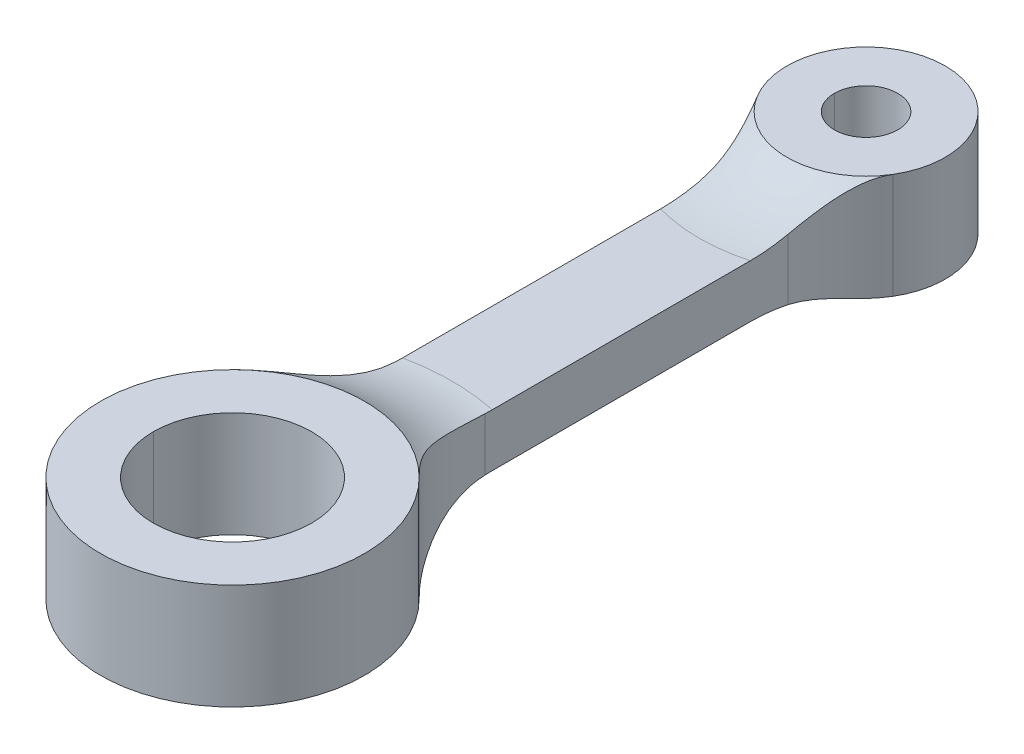
SolidWorks part; units mm, degrees
ref_plane "Płaszczyzna przednia" through (0, 0, 0) normal (0, 0, 1) x (1, 0, 0)
ref_plane "Płaszczyzna górna" through (0, 0, 0) normal (0, 1, 0) x (1, 0, 0)
ref_plane "Płaszczyzna prawa" through (0, 0, 0) normal (1, 0, 0) x (0, 0, -1)
sketch "Szkic1" [suppressed] plane through (0, 0, 0) normal (0, 1, 0) x (1, 0, 0)
  line L1 (0, 0) -> (45, 0)
  line L2 (0, 0) -> (0, 160)
  line L3 (0, 160) -> (45, 160)
  line L4 (45, 0) -> (45, 160)
  circle A0 centre (22.5, 145) radius 6
  circle A1 centre (22.5, 25) radius 15
  dimension "D5" = 12
  dimension "D6" = 30
  dimension "D1" = 45
  dimension "D2" = 160
  dimension "D3" = 25
  dimension "D4" = 120
extrude "Dodanie-wyciągnięcie1" [suppressed] add sketch "Szkic1" along normal blind 20
sketch "Szkic3" [suppressed] plane through (0, 0, 0) normal (1, 0, 0) x (0, 0, -1)
  line L0 (25, 20) -> (25, 0)
  line L1 (0, 20) -> (160, 20) construction
  line L2 (0, 0) -> (160, 0) construction
  line L3 (145, 20) -> (145, 0)
  line L4 (0, 20) -> (0, 0) construction
  dimension "D1" = 120
  dimension "D2" = 25
split line "Linia podziałowa1" [suppressed]
other "Grafika1"
other "Grafika (Zamknięta) -1"
sketch "Szkic5" plane through (0, 0, 0) normal (0, 1, 0) x (1, 0, 0)
  circle A0 centre (22.4625, 24.8988) radius 15
  circle A1 centre (22.4625, 144.8988) radius 6
  circle A2 centre (22.4625, 24.8988) radius 25
  circle A3 centre (22.4625, 144.8988) radius 15
  dimension "D1" = 30
  dimension "D2" = 12
  dimension "D4" = 10
  dimension "D5" = 50
  dimension "D6" = 9
  dimension "D3" = 120
extrude "Dodanie-wyciągnięcie2" add sketch "Szkic5" along normal blind 20
sketch "Szkic6" plane through (0, 0, 0) normal (0, 1, 0) x (1, 0, 0)
  line L0 (13.9625, 48.4095) -> (13.9625, 132.5396)
  line L1 (30.9625, 48.4095) -> (30.9625, 132.5396)
  line L2 (13.9625, 132.5396) -> (30.9625, 132.5396)
  line L3 (13.9625, 48.4095) -> (30.9625, 48.4095)
  line L4 (22.4625, 144.8988) -> (22.4625, 24.8988) construction
  circle A0 centre (22.4625, 24.8988) radius 25 construction
  circle A1 centre (22.4625, 144.8988) radius 15 construction
  dimension "D1" = 8.5
  dimension "D2" = 8.5
extrude "Dodanie-wyciągnięcie3" add sketch "Szkic6" along normal blind 10 from offset 5
sketch "Szkic9" plane through (0, 0, 0) normal (1, 0, 0) x (0, 0, -1)
  line L0 (24.8988, 20) -> (24.8988, 0)
  line L1 (39.8988, 20) -> (9.8988, 20) construction
  line L2 (49.8988, 0) -> (-0.1012, 0) construction
  line L3 (144.8988, 0) -> (144.8988, 20)
  line L4 (159.8988, 0) -> (129.8988, 0) construction
  line L5 (150.8988, 20) -> (138.8988, 20) construction
  line L6 (-0.1012, 20) -> (-0.1012, 0) construction
  dimension "D1" = 120
  dimension "D2" = 25
split line "Linia podziałowa2"
fillet "Zaokrąglenie1" radius 30 8 edges at (22.4625, 15, -129.8988) (22.4625, 5, -49.8988) (13.9625, 10, -48.4095) (13.9625, 10, -132.5396) (30.9625, 10, -132.5396) (22.4625, 5, -129.8988) (30.9625, 10, -48.4095) (22.4625, 15, -49.8988)
